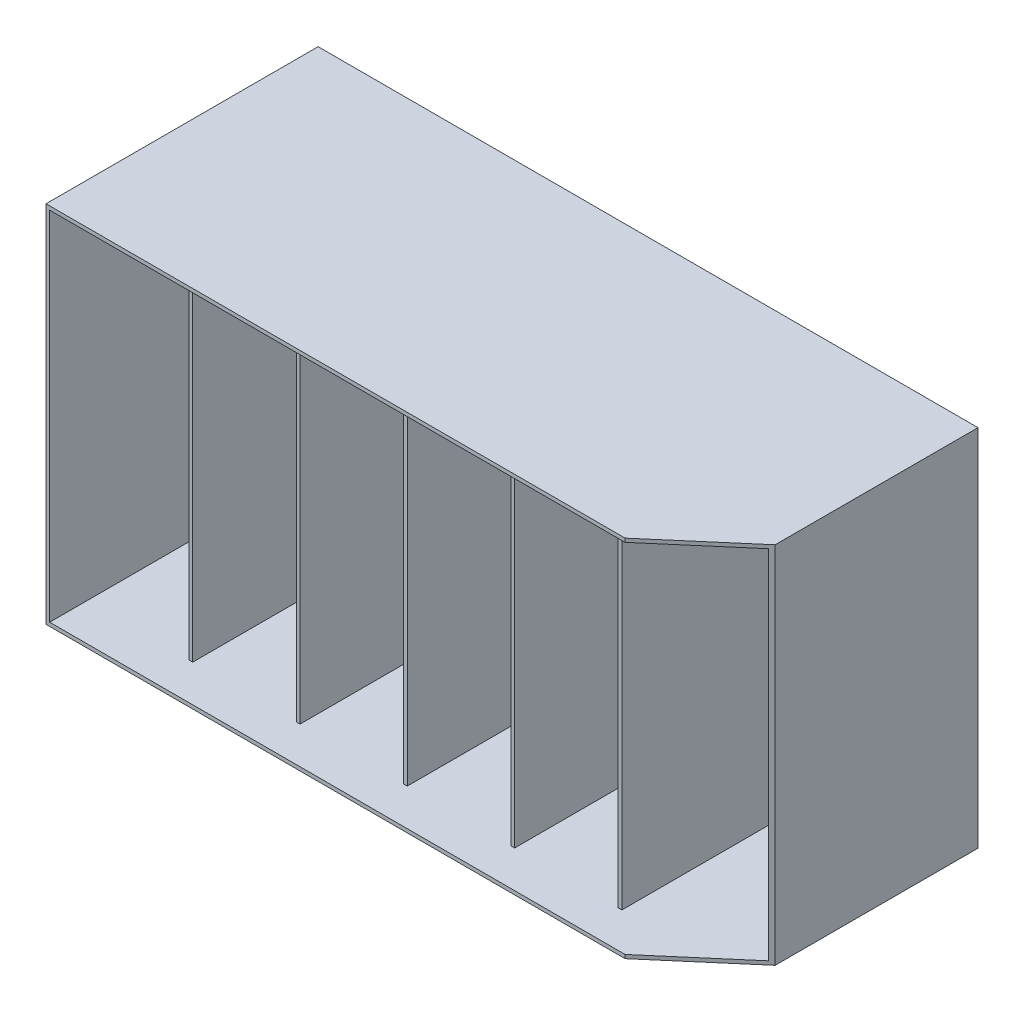
SolidWorks part; units mm, degrees
material "Custom Plastic"
ref_plane "X-Y Datum" through (0, 0, 0) normal (0, 0, 1) x (1, 0, 0)
ref_plane "X-Z Datum" through (0, 0, 0) normal (0, 1, 0) x (1, 0, 0)
ref_plane "Y-Z Datum" through (0, 0, 0) normal (1, 0, 0) x (0, 0, -1)
sketch "Sketch1" plane through (0, 0, 0) normal (0, 0, 1) x (1, 0, 0)
  line L0 (-282.702, 0) -> (282.702, 0) construction
  line L1 (-282.702, 154.6125) -> (282.702, 154.6125)
  line L2 (-282.702, 154.6125) -> (-282.702, -154.6125)
  line L3 (-282.702, -154.6125) -> (282.702, -154.6125)
  line L4 (282.702, 154.6125) -> (282.702, -154.6125)
  line L5 (-282.702, 154.6125) -> (282.702, -154.6125) construction
  line L6 (-282.702, -154.6125) -> (282.702, 154.6125) construction
  line L7 (-281.1145, 153.025) -> (-195.5145, 153.025) construction
  line L8 (-281.1145, 153.025) -> (-281.1145, -153.025) construction
  line L9 (-281.1145, -153.025) -> (-195.5145, -153.025) construction
  line L10 (-195.5145, 153.025) -> (-195.5145, -153.025) construction
  line L11 (-281.1145, 153.025) -> (-195.5145, -153.025) construction
  line L12 (-281.1145, -153.025) -> (-195.5145, 153.025) construction
  line L13 (-193.927, -154.6125) -> (-193.927, 154.6125)
  line L14 (-285.877, 157.7875) -> (285.877, 157.7875)
  line L15 (285.877, 157.7875) -> (285.877, -157.7875)
  line L16 (-285.877, -157.7875) -> (285.877, -157.7875)
  line L17 (-285.877, 157.7875) -> (-285.877, -157.7875)
  line L18 (-190.752, -154.6125) -> (-190.752, 154.6125)
  line L19 (-193.927, 0) -> (-190.752, 0) construction
  line L20 (-188.1505, 153.025) -> (-188.1505, -153.025) construction
  line L21 (-188.1505, 153.025) -> (-102.5505, 153.025) construction
  line L22 (-102.5505, 153.025) -> (-102.5505, -153.025) construction
  line L23 (-188.1505, -153.025) -> (-102.5505, -153.025) construction
  line L24 (-100.963, -154.6125) -> (-100.963, 154.6125)
  line L25 (-97.788, -154.6125) -> (-97.788, 154.6125)
  line L26 (-95.1865, 153.025) -> (-95.1865, -153.025) construction
  line L27 (-95.1865, 153.025) -> (-9.5865, 153.025) construction
  line L28 (-9.5865, 153.025) -> (-9.5865, -153.025) construction
  line L29 (-95.1865, -153.025) -> (-9.5865, -153.025) construction
  line L30 (-7.999, -154.6125) -> (-7.999, 154.6125)
  line L31 (-4.824, -154.6125) -> (-4.824, 154.6125)
  line L32 (-2.2225, 153.025) -> (-2.2225, -153.025) construction
  line L33 (-2.2225, 153.025) -> (83.3775, 153.025) construction
  line L34 (83.3775, 153.025) -> (83.3775, -153.025) construction
  line L35 (-2.2225, -153.025) -> (83.3775, -153.025) construction
  line L36 (84.965, -154.6125) -> (84.965, 154.6125)
  line L37 (88.14, -154.6125) -> (88.14, 154.6125)
  line L38 (90.7415, 153.025) -> (90.7415, -153.025) construction
  line L39 (90.7415, 153.025) -> (176.3415, 153.025) construction
  line L40 (176.3415, 153.025) -> (176.3415, -153.025) construction
  line L41 (90.7415, -153.025) -> (176.3415, -153.025) construction
  line L42 (177.929, -154.6125) -> (177.929, 154.6125)
  line L43 (181.104, -154.6125) -> (181.104, 154.6125)
  line L44 (-188.1505, -153.025) -> (-102.5505, 153.025) construction
  line L45 (-188.1505, 153.025) -> (-102.5505, -153.025) construction
  line L46 (-95.1865, -153.025) -> (-9.5865, 153.025) construction
  line L47 (-95.1865, 153.025) -> (-9.5865, -153.025) construction
  line L48 (-2.2225, -153.025) -> (83.3775, 153.025) construction
  line L49 (-2.2225, 153.025) -> (83.3775, -153.025) construction
  line L50 (90.7415, -153.025) -> (176.3415, 153.025) construction
  line L51 (90.7415, 153.025) -> (176.3415, -153.025) construction
  point P0 (0, 0)
  point P6 (-238.3145, 0)
  point P23 (-192.3395, 0)
  point P24 (-145.3505, 0)
  dimension "D1" = 306.05
  dimension "D2" = 85.6
  dimension "D3" = 1.5875
  dimension "D4" = 1.5875
  dimension "D5" = 1.5875
  dimension "D8" = 45.975
  dimension "D10" = 571.754
  dimension "D12" = 92.964
  dimension "D6" = 3.175
  dimension "D7" = 3.175
  dimension "D9" = 5
  dimension "D11" = 5
extrude "Boss-Extrude1" add sketch "Sketch1" along normal blind 3.175 contours L3 L13 L1 L2 | L3 L24 L1 L18 | L3 L18 L1 L13 | L14 L17 L16 L15 L1 L4 L3 L2 | L3 L30 L1 L25 | L3 L25 L1 L24 | L3 L36 L1 L31 | L3 L31 L1 L30 | L3 L42 L1 L37 | L3 L37 L1 L36 | L43 L3 L4 L1 | L3 L43 L1 L42 region at (-238.3145, 0, 0) region at (-192.3395, 0, 0) region at (-145.8575, 0, 0) region at (-99.3755, 0, 0) region at (-52.8935, 0, 0) region at (-6.4115, 0, 0) region at (40.0705, 0, 0) region at (86.5525, 0, 0) region at (133.0345, 0, 0) region at (179.5165, 0, 0) region at (231.903, 0, 0) region at (0, 157.1344, 0)
sketch "Sketch2" plane through (0, 0, 3.175) normal (0, 0, 1) x (1, 0, 0)
  line L0 (-193.927, -154.6125) -> (-193.927, 154.6125) construction
  line L1 (-100.963, -154.6125) -> (-100.963, 154.6125) construction
  line L2 (-190.752, -154.6125) -> (-190.752, 154.6125) construction
  line L3 (84.965, -154.6125) -> (84.965, 154.6125) construction
  line L4 (282.702, 154.6125) -> (-282.702, 154.6125)
  line L5 (282.702, -154.6125) -> (282.702, 154.6125)
  line L6 (-282.702, -154.6125) -> (282.702, -154.6125)
  line L7 (-282.702, 154.6125) -> (-282.702, -154.6125)
  line L8 (282.702, 154.6125) -> (-282.702, 154.6125)
  line L9 (282.702, -154.6125) -> (282.702, 154.6125)
  line L10 (-282.702, -154.6125) -> (282.702, -154.6125)
  line L11 (-282.702, 154.6125) -> (-282.702, -154.6125)
  line L12 (-285.877, -157.7875) -> (285.877, -157.7875)
  line L13 (-285.877, 157.7875) -> (-285.877, -157.7875)
  line L14 (285.877, 157.7875) -> (-285.877, 157.7875)
  line L15 (285.877, -157.7875) -> (285.877, 157.7875)
  line L16 (-285.877, -157.7875) -> (285.877, -157.7875)
  line L17 (-285.877, 157.7875) -> (-285.877, -157.7875)
  line L18 (285.877, 157.7875) -> (-285.877, 157.7875)
  line L19 (285.877, -157.7875) -> (285.877, 157.7875)
  line L20 (-4.824, -154.6125) -> (-4.824, 154.6125) construction
  line L21 (-7.999, -154.6125) -> (-7.999, 154.6125) construction
  line L22 (-97.788, -154.6125) -> (-97.788, 154.6125) construction
  line L23 (181.104, -154.6125) -> (181.104, 154.6125) construction
  line L24 (177.929, -154.6125) -> (177.929, 154.6125) construction
  line L25 (88.14, -154.6125) -> (88.14, 154.6125) construction
  line L26 (-193.927, -154.6125) -> (-193.927, 154.6125)
  line L27 (-100.963, -154.6125) -> (-100.963, 154.6125)
  line L28 (-190.752, -154.6125) -> (-190.752, 154.6125)
  line L29 (84.965, -154.6125) -> (84.965, 154.6125)
  line L30 (-4.824, -154.6125) -> (-4.824, 154.6125)
  line L31 (-7.999, -154.6125) -> (-7.999, 154.6125)
  line L32 (-97.788, -154.6125) -> (-97.788, 154.6125)
  line L33 (181.104, -154.6125) -> (181.104, 154.6125)
  line L34 (177.929, -154.6125) -> (177.929, 154.6125)
  line L35 (88.14, -154.6125) -> (88.14, 154.6125)
  line M9 (285.877, 157.7875) -> (-285.877, 157.7875)
  line M10 (-285.877, 157.7875) -> (-285.877, -157.7875)
  line M11 (-285.877, -157.7875) -> (285.877, -157.7875)
  line M12 (285.877, -157.7875) -> (285.877, 157.7875)
  dimension "D1" = 0
  dimension "D2" = 0
extrude "Boss-Extrude2" add sketch "Sketch2" along normal blind 200.6 contours L11 L8 L9 L10 M12 M9 M10 M11 | L10 L28 L8 L26 | L10 L32 L8 L27 | L31 L10 L30 L8 | L10 L35 L8 L29 | L34 L10 L33 L8 region at (179.5165, 0, 3.175) region at (86.5525, 0, 3.175) region at (-6.4115, 0, 3.175) region at (-99.3755, 0, 3.175) region at (-192.3395, 0, 3.175) region at (-285.2239, 0, 3.175)
sketch "Sketch3" plane through (0, 0, 203.775) normal (0, 0, 1) x (1, 0, 0)
  line L0 (-193.927, -154.6125) -> (-193.927, 154.6125) construction
  line L1 (-100.963, -154.6125) -> (-100.963, 154.6125) construction
  line L2 (-190.752, -154.6125) -> (-190.752, 154.6125) construction
  line L3 (84.965, -154.6125) -> (84.965, 154.6125) construction
  line L4 (282.702, 154.6125) -> (-282.702, 154.6125)
  line L5 (282.702, -154.6125) -> (282.702, 154.6125)
  line L6 (-282.702, -154.6125) -> (282.702, -154.6125)
  line L7 (-282.702, 154.6125) -> (-282.702, -154.6125)
  line L8 (282.702, 154.6125) -> (-282.702, 154.6125)
  line L9 (282.702, -154.6125) -> (282.702, 154.6125)
  line L10 (-282.702, -154.6125) -> (282.702, -154.6125)
  line L11 (-282.702, 154.6125) -> (-282.702, -154.6125)
  line L12 (-285.877, -157.7875) -> (285.877, -157.7875)
  line L13 (-285.877, 157.7875) -> (-285.877, -157.7875)
  line L14 (285.877, 157.7875) -> (-285.877, 157.7875)
  line L15 (285.877, -157.7875) -> (285.877, 157.7875)
  line L16 (-285.877, -157.7875) -> (285.877, -157.7875)
  line L17 (-285.877, 157.7875) -> (-285.877, -157.7875)
  line L18 (285.877, 157.7875) -> (-285.877, 157.7875)
  line L19 (285.877, -157.7875) -> (285.877, 157.7875)
  line L20 (-4.824, -154.6125) -> (-4.824, 154.6125) construction
  line L21 (-7.999, -154.6125) -> (-7.999, 154.6125) construction
  line L22 (-97.788, -154.6125) -> (-97.788, 154.6125) construction
  line L23 (181.104, -154.6125) -> (181.104, 154.6125) construction
  line L24 (177.929, -154.6125) -> (177.929, 154.6125) construction
  line L25 (88.14, -154.6125) -> (88.14, 154.6125) construction
  line L26 (-193.927, -154.6125) -> (-193.927, 154.6125)
  line L27 (-100.963, -154.6125) -> (-100.963, 154.6125)
  line L28 (-190.752, -154.6125) -> (-190.752, 154.6125)
  line L29 (84.965, -154.6125) -> (84.965, 154.6125)
  line L30 (-4.824, -154.6125) -> (-4.824, 154.6125)
  line L31 (-7.999, -154.6125) -> (-7.999, 154.6125)
  line L32 (-97.788, -154.6125) -> (-97.788, 154.6125)
  line L33 (181.104, -154.6125) -> (181.104, 154.6125)
  line L34 (177.929, -154.6125) -> (177.929, 154.6125)
  line L35 (88.14, -154.6125) -> (88.14, 154.6125)
  line M9 (88.14, 154.6125) -> (177.929, 154.6125)
  line M11 (177.929, -154.6125) -> (88.14, -154.6125)
  line M13 (-4.824, 154.6125) -> (84.965, 154.6125)
  line M15 (84.965, -154.6125) -> (-4.824, -154.6125)
  line M17 (-97.788, 154.6125) -> (-7.999, 154.6125)
  line M19 (-7.999, -154.6125) -> (-97.788, -154.6125)
  line M21 (-190.752, 154.6125) -> (-100.963, 154.6125)
  line M23 (-100.963, -154.6125) -> (-190.752, -154.6125)
  line M25 (-282.702, 154.6125) -> (-193.927, 154.6125)
  line M27 (-193.927, -154.6125) -> (-282.702, -154.6125)
  line M28 (-282.702, -154.6125) -> (-282.702, 154.6125)
  line M30 (181.104, 154.6125) -> (282.702, 154.6125)
  line M31 (282.702, 154.6125) -> (282.702, -154.6125)
  line M32 (282.702, -154.6125) -> (181.104, -154.6125)
  line M33 (285.877, -157.7875) -> (285.877, 157.7875)
  line M34 (285.877, 157.7875) -> (-285.877, 157.7875)
  line M35 (-285.877, 157.7875) -> (-285.877, -157.7875)
  line M36 (-285.877, -157.7875) -> (285.877, -157.7875)
  dimension "D1" = 0
  dimension "D2" = 0
extrude "Boss-Extrude3" add sketch "Sketch3" along normal blind 32 contours L10 L8 M36 M33 M34 M35 M27 M28 M25 M21 M17 M13 M9 M30 M31 M32 M11 M15 M19 M23 region at (-285.2239, 0, 203.775)
sketch "Sketch4" plane through (0, -157.7875, 0) normal (0, -1, 0) x (1, 0, 0)
  line L0 (215.877, 235.775) -> (285.877, 175.775)
  line L1 (-285.877, 235.775) -> (285.877, 235.775) construction
  line L2 (285.877, 235.775) -> (285.877, 0) construction
  line M3 (285.877, 0) -> (285.877, 235.775)
  line M4 (285.877, 235.775) -> (-285.877, 235.775)
  dimension "D1" = 60
  dimension "D2" = 70
extrude "Cut-Extrude1" cut sketch "Sketch4" against normal through all contours L0 M4 M3 region at (262.5437, -157.7875, 215.775)
sketch "Sketch5" plane through (181.104, 0, 0) normal (1, 0, 0) x (0, 0, -1)
  line L0 (-3.175, 0) -> (-117.475, 0)
  line L1 (-3.175, -154.6125) -> (-3.175, 154.6125) construction
  line L2 (-117.475, 154.6125) -> (-117.475, 0)
  line L3 (-203.775, 154.6125) -> (-3.175, 154.6125) construction
  line L4 (-117.475, -154.6125) -> (-117.475, 0)
  line L5 (-203.775, -154.6125) -> (-3.175, -154.6125) construction
  dimension "D1" = 114.3
